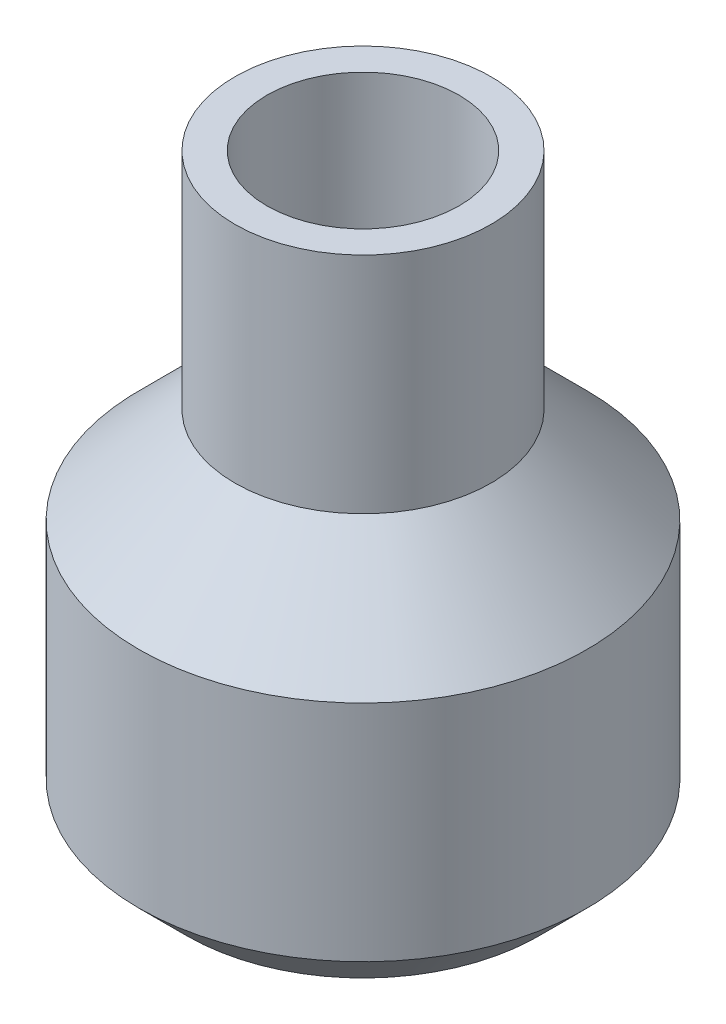
SolidWorks part; units mm, degrees
ref_plane "Front Plane" through (0, 0, 0) normal (0, 0, 1) x (1, 0, 0)
ref_plane "Top Plane" through (0, 0, 0) normal (0, 1, 0) x (1, 0, 0)
ref_plane "Right Plane" through (0, 0, 0) normal (1, 0, 0) x (0, 0, -1)
sketch "Sketch1" plane through (0, 0, 0) normal (0, 1, 0) x (1, 0, 0)
  circle A0 centre (0, 0) radius 4
  circle A1 centre (0, 0) radius 3
  dimension "D1" = 8
  dimension "D2" = 6
extrude "Boss-Extrude1" add sketch "Sketch1" along normal blind 10
sketch "Sketch2" plane through (0, 0, 0) normal (0, 1, 0) x (1, 0, 0)
  circle A0 centre (0, 0) radius 7
  dimension "D1" = 14
extrude "Boss-Extrude2" add sketch "Sketch2" against normal blind 8.5
sketch "Sketch3" plane through (0, -8.5, 0) normal (0, -1, 0) x (1, 0, 0)
  circle A0 centre (0, 0) radius 6
  dimension "D1" = 12
extrude "Cut-Extrude1" cut sketch "Sketch3" against normal offset from surface (6.5 mm away) 2 up to face at (0, 0, 4)
sketch "Sketch4" plane through (0, 0, 0) normal (0, 1, 0) x (1, 0, 0)
  circle A0 centre (0, 0) radius 3
extrude "Cut-Extrude2" cut sketch "Sketch4" against normal through all
ref_plane "Plane1" through (0, -8.5, 0) normal (0, -1, 0) x (-1, 0, 0)
sketch "Sketch5" plane through (0, -8.5, 0) normal (0, -1, 0) x (-1, 0, 0)
  circle A1 centre (0, 0) radius 5
  circle A3 centre (0, 0) radius 6
  dimension "D1" = 1
extrude "Boss-Extrude3" add sketch "Sketch5" against normal blind 0.5
chamfer "Chamfer2" distance 1.5 angle 45 1 edges at (0, -8.5, 7)
chamfer "Chamfer3" distance 1.2 angle 45 1 edges at (0, -8, -6)
fillet "Fillet1" radius 2 1 edges at (0, -7.8, 5)
chamfer "Chamfer4" distance 3 angle 45 1 edges at (0, 0, 4)
